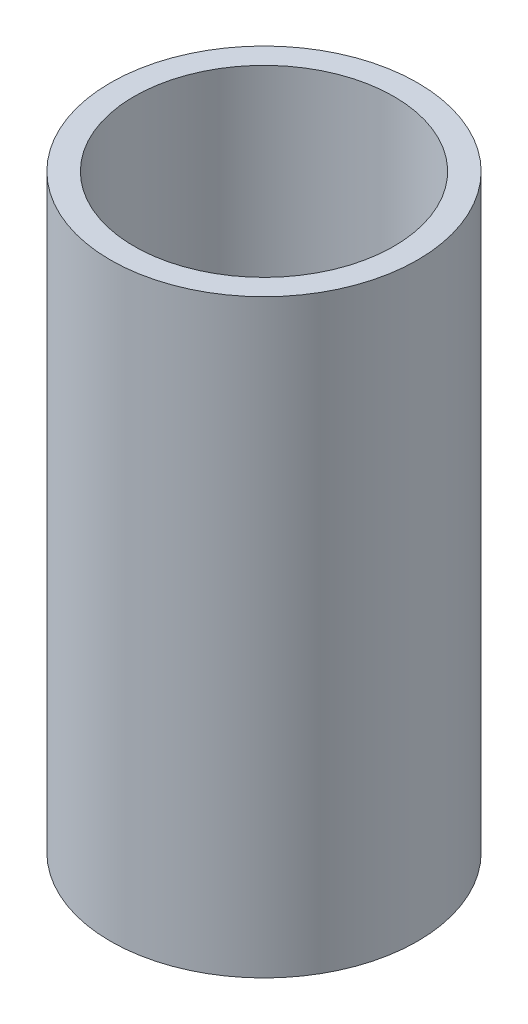
SolidWorks part; units mm, degrees
ref_plane "Front Plane" through (0, 0, 0) normal (0, 0, 1) x (1, 0, 0)
ref_plane "Top Plane" through (0, 0, 0) normal (0, 1, 0) x (1, 0, 0)
ref_plane "Right Plane" through (0, 0, 0) normal (1, 0, 0) x (0, 0, -1)
sketch "Sketch1" plane through (0, 0, 0) normal (0, 1, 0) x (1, 0, 0)
  circle A0 centre (0, 0) radius 32.5
  dimension "SLEEVE_OD" = 65
extrude "Boss-Extrude1" add sketch "Sketch1" along normal blind 124.8815
sketch "Sketch2" plane through (0, 0, 0) normal (0, 1, 0) x (1, 0, 0)
  circle A0 centre (0, 0) radius 27.4879
  dimension "BORE_D" = 54.9757
extrude "Cut-Extrude1" cut sketch "Sketch2" along normal through all
chamfer "Chamfer1" distance 3.0983 angle 45 rebuild error yes
